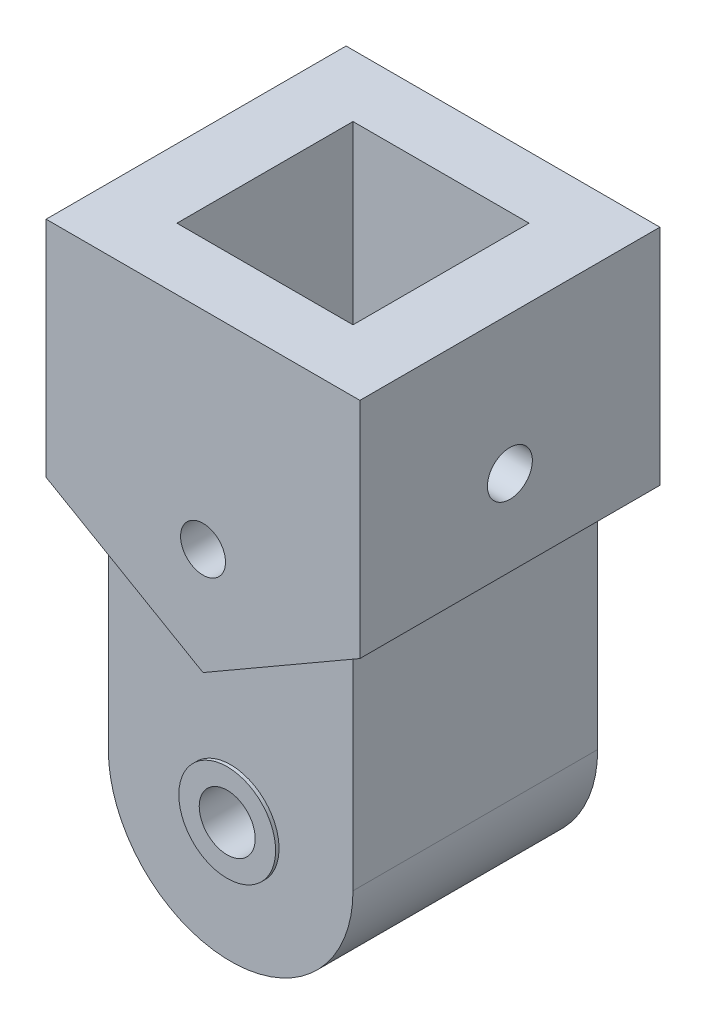
SolidWorks part; units mm, degrees
material "PETG"
ref_plane "Front Plane" through (0, 0, 0) normal (0, 0, 1) x (1, 0, 0)
ref_plane "Top Plane" through (0, 0, 0) normal (0, 1, 0) x (1, 0, 0)
ref_plane "Right Plane" through (0, 0, 0) normal (1, 0, 0) x (0, 0, -1)
sketch "Sketch1" plane through (0, 0, 0) normal (0, 1, 0) x (1, 0, 0)
  line L1 (-12.7375, -12.7375) -> (12.7375, -12.7375)
  line L2 (-12.7375, -12.7375) -> (-12.7375, 12.7375)
  line L3 (-12.7375, 12.7375) -> (12.7375, 12.7375)
  line L4 (12.7375, -12.7375) -> (12.7375, 12.7375)
  line L5 (-17.7, -17.7) -> (17.7, -17.7)
  line L6 (-17.7, -17.7) -> (-17.7, 17.7)
  line L7 (-17.7, 17.7) -> (17.7, 17.7)
  line L8 (17.7, -17.7) -> (17.7, 17.7)
  point P8 (0, -17.7)
  point P9 (0, -12.7375)
  point P12 (-17.7, 0)
  point P13 (-12.7375, 0)
  dimension "D1" = 25.475
  dimension "D2" = 35.4
extrude "Boss-Extrude1" add sketch "Sketch1" along normal blind 50.0375
extrude "Boss-Extrude2" add sketch "Sketch1<3>" against normal blind 9.9625 contours L1 L4 L3 L2 | L5 L8 L7 L6 L4 L1 L2 L3 region at (0, 0, 0) region at (-17.1994, 0, 0)
sketch "Sketch1<3>" plane through (0, 0, 0) normal (0, 1, 0) x (1, 0, 0) same geometry as "Sketch1"
sketch "Sketch2" plane through (0, 0, -17.7) normal (0, 0, 1) x (1, 0, 0)
  line L1 (17.7, 50.0375) -> (17.7, -9.9625) construction
  line L4 (-17.7, -9.9625) -> (17.7, -9.9625) construction
  line L5 (-17.7, -15.9125) -> (-17.7, -9.9625)
  line L6 (17.7, -9.9625) -> (17.7, -15.9125)
  line L7 (17.7, -9.9625) -> (-17.7, -9.9625)
  circle A0 centre (0, -15.9625) radius 4.05
  circle A2 centre (0, -15.9625) radius 11 construction
  arc A3 (17.7, -15.9125) -> (-17.7, -15.9125) centre (0, -15.9125) cw
  dimension "D1" = 8.1
  dimension "D3" = 22
  dimension "D2" = 6
  dimension "D4" = 5.95
extrude "Boss-Extrude5" add sketch "Sketch2" along normal up to surface (35.4 mm away) up to face at (0, 20.0375, 17.7)
ref_plane "Plane1" through (0, -33.6125, 0) normal (0, -1, 0) x (-1, 0, 0)
sketch "Sketch3" plane through (0, -33.6125, 0) normal (0, -1, 0) x (-1, 0, 0)
  circle A0 centre (0, 0) radius 3.15
  dimension "D1" = 6.3
extrude "Cut-Extrude1" cut sketch "Sketch3" against normal through all
sketch "Sketch4" plane through (0, -33.6125, 0) normal (0, -1, 0) x (-1, 0, 0)
  circle A0 centre (0, 0) radius 5.5
  dimension "D1" = 11
extrude "Cut-Extrude2" cut sketch "Sketch4" against normal offset from surface (25.6125 mm away) 8 up to face at (0, 0, 3.15)
sketch "Sketch5" plane through (0, 0, 17.7) normal (0, 0, 1) x (1, 0, 0)
  circle A0 centre (0, -15.9625) radius 7
  circle A1 centre (0, -15.9625) radius 4.05 construction
  circle M6 centre (0, -15.9625) radius 4.05
  dimension "D1" = 14
extrude "Boss-Extrude6" add sketch "Sketch5" along normal blind 0.5 contours A0 M6 region at (-6.802, -15.9625, 17.7)
mirror "Mirror1" about plane through (0, 0, 0) normal (0, 0, 1) of "Boss-Extrude6"
sketch "Sketch6" plane through (0, 0, 17.7) normal (0, 0, 1) x (1, 0, 0)
  line L5 (8.875, -31.2845) -> (52.1763, -6.2845) construction
  line L6 (-8.875, -0.5405) -> (34.4263, 24.4595) construction
  line L7 (52.1763, -6.2845) -> (34.4263, 24.4595) construction
  line L8 (0, -16) -> (0, -79.4793) construction
  line L9 (17.7, 50.0375) -> (17.7, -15.9125) construction
  line L10 (17.7, 14.8025) -> (-17.7, 14.8025)
  line L11 (17.7, 14.8025) -> (17.7, 50.0375)
  line L12 (17.7, 50.0375) -> (-17.7, 50.0375)
  line L13 (-17.7, 14.8025) -> (-17.7, 50.0375)
  line L14 (17.7, 14.8025) -> (0, 4.5834)
  line L15 (0, 4.5834) -> (-17.7, 14.8025)
  circle A1 centre (0, -15.9125) radius 17.75
  arc A2 (-17.7, -15.9125) -> (17.7, -15.9125) centre (0, -15.9125) ccw construction
  line M4 (-17.7, 50.0375) -> (-17.7, -15.9125)
  line M6 (17.7, -15.9125) -> (17.7, 50.0375)
  line M7 (17.7, 50.0375) -> (-17.7, 50.0375)
  dimension "D1" = 50
  dimension "D2" = 120
  dimension "D3" = 35.5
extrude "Boss-Extrude7" add sketch "Sketch6" along normal blind 4 contours L14 L10 M4 | L10 M6 M7 M4 region at (0, 11.3962, 17.7) region at (0, 32.42, 17.7)
sketch "Sketch7" plane through (0, 0, 21.7) normal (0, 0, 1) x (1, 0, 0)
  line L0 (17.7, 50.0375) -> (-17.7, 50.0375) construction
  line L1 (17.7, 20.0375) -> (0, 20.0375) construction
  line L2 (17.7, 14.8025) -> (17.7, 50.0375) construction
  line L3 (0, 20.0375) -> (-17.7, 20.0375) construction
  line L4 (-17.7, 50.0375) -> (-17.7, 14.8025) construction
  circle A0 centre (0, 20.0375) radius 3.25
  dimension "D1" = 30
  dimension "D2" = 6.5
extrude "Cut-Extrude3" cut sketch "Sketch7" against normal up to next
mirror "Mirror2" about plane through (0, 0, 0) normal (0, 0, 1) of "Boss-Extrude7", "Cut-Extrude3"
sketch "Sketch9" plane through (0, 0, 0) normal (0, 0, 1) x (1, 0, 0)
  line L0 (-17.7, 14.8025) -> (-22.7, 17.6893)
  line L1 (0, 4.5834) -> (-17.7, 14.8025) construction
  line L3 (-17.7, 14.8025) -> (-17.7, 50.0375)
  line L4 (-17.7, 50.0375) -> (-22.7, 50.0375)
  line L5 (-22.7, 17.6893) -> (-22.7, 50.0375)
  line L6 (0, 0) -> (0, 50000) construction
  line L7 (22.7, 17.6893) -> (22.7, 50.0375)
  line L8 (17.7, 50.0375) -> (22.7, 50.0375)
  line L9 (17.7, 14.8025) -> (17.7, 50.0375)
  line L10 (17.7, 14.8025) -> (22.7, 17.6893)
  dimension "D1" = 5
extrude "Boss-Extrude9" add sketch "Sketch9" along normal up to surface and the other way up to surface up to face at (3.25, 20.0375, 21.7) other way up to face at (3.25, 20.0375, -21.7)
sketch "Sketch10" plane through (0, 0, 0) normal (-1, 0, 0) x (0, 0, 1)
  line L0 (21.7, 50.0375) -> (-21.7, 50.0375) construction
  circle A0 centre (0, 30.0375) radius 3.25
  dimension "D1" = 6.5
  dimension "D2" = 20
extrude "Cut-Extrude4" cut sketch "Sketch10" against normal through all both and the other way through all
equation "\"tol_dia_id_intfc\" = 0.0500mm ' For hole diameters - Interference fit"
equation "\"tol_dia_id_slip\"  = 0.0750mm ' For hole diameters - Slip fit"
equation "\"tol_dia_id_clear\" = 0.1000mm ' For hole diameters - Clearance fit"
equation "\"tol_dia_od_intfc\" = 0.0500mm ' For shaft diameters - Interference fit"
equation "\"tol_dia_od_slip\"  = 0.0750mm ' For shaft diameters - Slip fit"
equation "\"tol_dia_od_clear\" = 0.1000mm ' For shaft diameters - Clearance fit"
equation "\"tol_general_intfc\"= 0.0250mm ' For general parts (Horiz) - Interference fit"
equation "\"tol_general_slip\" = 0.0375mm ' For general parts (Horiz) - Slip fit"
equation "\"tol_general_clear\"= 0.0500mm ' For general parts (Horiz) - Clearance fit"
equation "\"tol_layer_intfc\"  = 0.0250mm ' For all parts (Vert) - Interference fit"
equation "\"tol_layer_slip\"   = 0.0375mm ' For all parts (Vert) - Slip fit"
equation "\"tol_layer_clear\"  = 0.0500mm ' For all parts (Vert) - Clearance fit"
equation "\"tol_corner_rad\"   = 0.100mm ' For corners that fit into other parts"
equation "\"D1@Sketch1\"=25.40mm+\"tol_general_slip\"*2"
equation "\"D2@Sketch1\"=25.4+10"
equation "\"D1@Boss-Extrude1\"= 50.00mm + \"tol_layer_slip\""
equation "\"D1@Boss-Extrude2\"=10.00mm-\"tol_layer_slip\""
equation "\"D1@Sketch2\"=8.00mm+\"tol_dia_id_clear\""
equation "\"D4@Sketch2\"=6.00mm-\"tol_dia_od_clear\"/2"
equation "\"D3@Sketch6\"=25.4+10+\"tol_general_clear\"*2"
